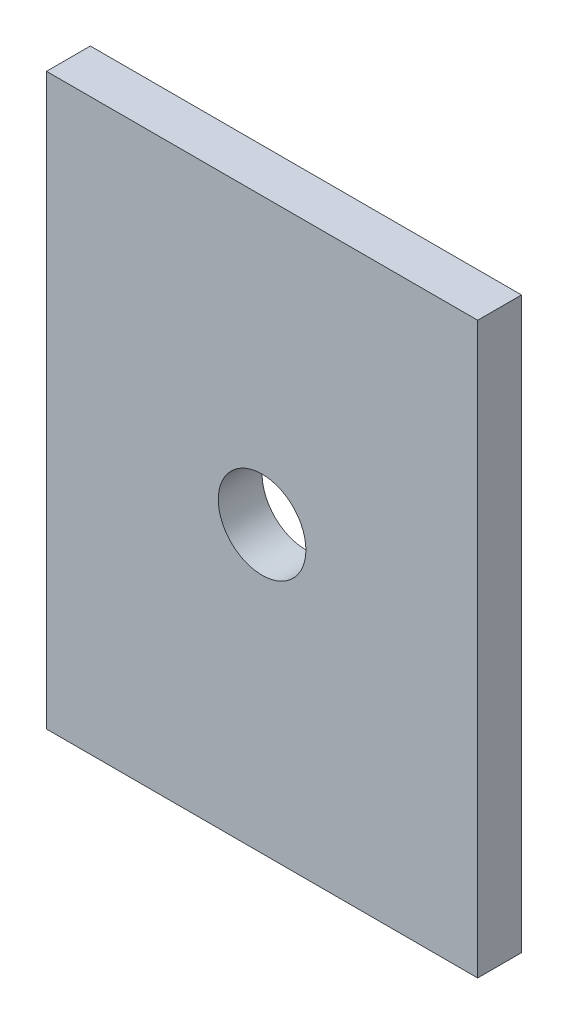
SolidWorks part; units mm, degrees
ref_plane "Front Plane" through (0, 0, 0) normal (0, 0, 1) x (1, 0, 0)
ref_plane "Top Plane" through (0, 0, 0) normal (0, 1, 0) x (1, 0, 0)
ref_plane "Right Plane" through (0, 0, 0) normal (1, 0, 0) x (0, 0, -1)
sketch "Sketch1" plane through (0, 0, 0) normal (0, 0, 1) x (1, 0, 0)
  line L1 (-4.92, -6.5) -> (4.92, -6.5)
  line L2 (-4.92, -6.5) -> (-4.92, 6.5)
  line L3 (-4.92, 6.5) -> (4.92, 6.5)
  line L4 (4.92, -6.5) -> (4.92, 6.5)
  line L5 (-4.92, -6.5) -> (4.92, 6.5) construction
  line L6 (-4.92, 6.5) -> (4.92, -6.5) construction
  point P0 (0, 0)
extrude "Boss-Extrude1" add sketch "Sketch1" along normal blind 1
sketch "Sketch2" plane through (0, 0, 1) normal (0, 0, 1) x (1, 0, 0)
  circle A0 centre (0, 0) radius 1
extrude "Cut-Extrude1" cut sketch "Sketch2" against normal through all
